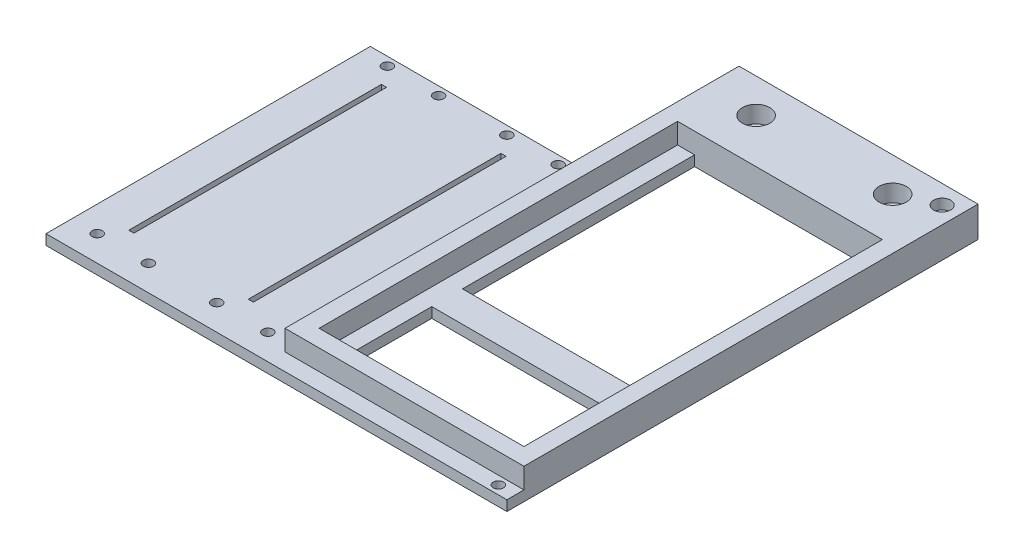
SolidWorks part; units mm, degrees
ref_plane "Front Plane" through (0, 0, 0) normal (0, 0, 1) x (1, 0, 0)
ref_plane "Top Plane" through (0, 0, 0) normal (0, 1, 0) x (1, 0, 0)
ref_plane "Right Plane" through (0, 0, 0) normal (1, 0, 0) x (0, 0, -1)
sketch "Sketch1" plane through (0, 0, 0) normal (0, 1, 0) x (1, 0, 0)
  line L0 (-30, 40) -> (30, 40)
  line L1 (-35, -65) -> (35, -65)
  line L2 (-35, -65) -> (-35, 65)
  line L3 (-35, 65) -> (35, 65)
  line L4 (35, -65) -> (35, 65)
  line L5 (-35, -65) -> (35, 65) construction
  line L6 (-35, 65) -> (35, -65) construction
  line L7 (-35, -65) -> (-30, -65)
  line L8 (-35, -65) -> (-35, 65)
  line L9 (-35, 65) -> (-30, 65)
  line L10 (-30, -65) -> (-30, 65)
  line L11 (35, 65) -> (30, 65)
  line L12 (35, 65) -> (35, -65)
  line L13 (35, -65) -> (30, -65)
  line L14 (30, 65) -> (30, -65)
  line L15 (-30, -65) -> (30, -65)
  line L16 (-30, -65) -> (-30, -60)
  line L17 (-30, -60) -> (30, -60)
  line L18 (30, -65) -> (30, -60)
  line L19 (-95, 22.5) -> (-75, 22.5) construction
  line L20 (-35, -65) -> (-100, -65)
  line L21 (-35, -65) -> (-35, 25)
  line L22 (-35, 25) -> (-100, 25)
  line L23 (-100, -65) -> (-100, 25)
  line L24 (-95, -65) -> (-75, -65)
  line L25 (-95, -65) -> (-95, 25)
  line L26 (-95, 25) -> (-75, 25)
  line L27 (-75, -65) -> (-75, 25)
  line L28 (-85, 22.5) -> (-85, 25) construction
  line L29 (-100, -20) -> (-35, -20) construction
  line L30 (-67.5, -65) -> (-67.5, 25) construction
  line L31 (-40, 25) -> (-60, 25)
  line L32 (-60, -65) -> (-60, 25)
  line L33 (-40, -65) -> (-60, -65)
  line L34 (-40, -65) -> (-40, 25)
  line L35 (-53.75, -57) -> (-53.75, 17)
  line L36 (-88.75, -57) -> (-87.25, -57)
  line L37 (-88.75, -57) -> (-88.75, 17)
  line L38 (-88.75, 17) -> (-87.25, 17)
  line L39 (-87.25, -57) -> (-87.25, 17)
  line L40 (-88.75, -57) -> (-87.25, 17) construction
  line L41 (-88.75, 17) -> (-87.25, -57) construction
  line L42 (-53.75, -57) -> (-52.25, -57)
  line L43 (-52.25, -57) -> (-52.25, 17)
  line L44 (-53.75, 17) -> (-52.25, 17)
  line L46 (-25, -55) -> (25, -55)
  line L47 (-25, -55) -> (-25, 55)
  line L48 (-25, 55) -> (25, 55)
  line L49 (25, -55) -> (25, 55)
  line L50 (-25, -55) -> (25, 55) construction
  line L51 (-25, 55) -> (25, -55) construction
  line L52 (-25, -32) -> (25, -32)
  line L53 (-25, -32) -> (-25, -23)
  line L54 (-25, -23) -> (25, -23)
  line L55 (25, -32) -> (25, -23)
  line L56 (-30, 65) -> (25, 65)
  line L57 (-30, 65) -> (-30, 45)
  line L58 (-30, 45) -> (25, 45)
  line L59 (25, 65) -> (25, 45)
  line L60 (25, 45) -> (30, 45)
  line L61 (25, 45) -> (25, 55)
  line L62 (25, 55) -> (30, 55)
  line L63 (30, 45) -> (30, 55)
  circle A0 centre (-92.5, 22.5) radius 1.5
  circle A1 centre (-77.5, 22.5) radius 1.5
  circle A2 centre (-77.5, -62.5) radius 1.5
  circle A3 centre (-92.5, -62.5) radius 1.5
  circle A4 centre (-42.5, -62.5) radius 1.5
  circle A5 centre (-57.5, -62.5) radius 1.5
  circle A6 centre (-57.5, 22.5) radius 1.5
  circle A7 centre (-42.5, 22.5) radius 1.5
  point P0 (0, 0)
  point P49 (-88, -20)
  point P54 (0, 0)
  dimension "D11" = 2.5
  dimension "D1" = 70
  dimension "D2" = 130
  dimension "D3" = 5
  dimension "D4" = 5
  dimension "D5" = 5
  dimension "D6" = 100
  dimension "D7" = 90
  dimension "D8" = 135
  dimension "D9" = 5
  dimension "D10" = 90
  dimension "D12" = 2.5
  dimension "D13" = 20
  dimension "D14" = 15
  dimension "D15" = 1.5
  dimension "D16" = 74
  dimension "D17" = 7
  dimension "D18" = 2
  dimension "D19" = 5
  dimension "D20" = 5
  dimension "D21" = 9
  dimension "D22" = 23
  dimension "D23" = 5
extrude "Boss-Extrude1" add sketch "Sketch1" along normal blind 9 contours L1 L10 L3 L2 | L17 L10 L1 L14 | L3 L14 L1 L4 | L59 L3 L10 L58 L47 L48 | L47 L58 L49 L48 | L59 L62 L14 L3 | L62 L49 L60 L14 region at (-32.5, 0, 0) region at (0, 0, 62.5) region at (-4.5833, 0, -59.1667) region at (0, 0, -50) region at (32.5, 0, 0) region at (27.5, 0, -50) region at (27.5, 0, -60)
extrude "Boss-Extrude2" add sketch "Sketch1<3>" along normal blind 3 contours L10 L17 L14 L0 | L14 L3 L10 L0 | L20 L25 L22 L23 | L20 L27 L22 L25 A1 A0 A2 A3 | L20 L32 L22 L27 | L20 L34 L22 L32 A5 A4 A6 A7 | L34 L20 L2 L22 | L54 L47 L52 L49 | L58 L10 L0 L47 | L60 L49 L0 L14 region at (-27.5, 0, -42.5) region at (-27.5, 0, -38.8338) region at (27.5, 0, -42.5) region at (0, 0, 27.5) region at (-37.5, 0, 20) region at (27.5, 0, -60) region at (-49.7995, 0, 20) region at (-67.5, 0, 20) region at (-84.7995, 0, 20) region at (-97.5, 0, 20)
sketch "Sketch1<3>" plane through (0, 0, 0) normal (0, 1, 0) x (1, 0, 0) same geometry as "Sketch1"
sketch "Sketch2" plane through (0, 0, 0) normal (0, 1, 0) x (1, 0, 0)
  line L0 (-35, -65) -> (35, -65) construction
  line L1 (-35, -65) -> (-100, -65) construction
  line L2 (-35, -65) -> (35, -65)
  line L3 (-35, -65) -> (-100, -65)
  line L4 (35, -67.5) -> (16.5103, -67.5) construction
  line L5 (35, -65) -> (-100, -65)
  line L6 (35, -65) -> (35, -70)
  line L7 (35, -70) -> (-100, -70)
  line L8 (-100, -65) -> (-100, -70)
  circle A0 centre (30, -67.5) radius 1.5
  dimension "D2" = 5
  dimension "D1" = 5
extrude "Boss-Extrude3" add sketch "Sketch2" along normal blind 3 contours L3 L8 L7 L6 L2 region at (-33.1614, 0, 67.5)
sketch "Sketch3" plane through (0, 9, 0) normal (0, 1, 0) x (1, 0, 0)
  line L0 (0, 65) -> (0, 25.4695) construction
  line L1 (-35, 65) -> (35, 65) construction
  line L2 (-35, 65) -> (35, 65)
  line L3 (-22.9804, 58) -> (23.7883, 58) construction
  line L4 (35, -65) -> (35, 65) construction
  line L5 (35, -65) -> (35, 65)
  line L6 (30, 60) -> (30, 65) construction
  line L7 (35, 60) -> (25, 60)
  line L8 (35, 60) -> (35, 65)
  line L9 (35, 65) -> (25, 65)
  line L10 (25, 60) -> (25, 65)
  circle A0 centre (-20, 58) radius 4
  circle A1 centre (20, 58) radius 4
  circle A2 centre (30, 62.5) radius 1.5
  circle A3 centre (30, 62.5) radius 2.5
  dimension "D1" = 40
  dimension "D2" = 8
  dimension "D3" = 7
  dimension "D4" = 5
  dimension "D5" = 10
extrude "Cut-Extrude1" cut sketch "Sketch3" against normal blind 5 contours A0 | A1
extrude "Cut-Extrude2" cut sketch "Sketch3<3>" against normal blind 20 contours A2 region at (30, 9, -62.5)
sketch "Sketch3<3>" plane through (0, 9, 0) normal (0, 1, 0) x (1, 0, 0) same geometry as "Sketch3"
sketch "Sketch4" plane through (0, 0, -65) normal (0, 0, -1) x (-1, 0, 0)
  line L4 (-35, 9) -> (-35, 0)
  line L5 (-35, 0) -> (35, 0)
  line L6 (35, 0) -> (35, 9)
  line L7 (35, 9) -> (-35, 9)
  line L8 (-35, 9) -> (-35, 0)
  line L9 (-35, 0) -> (35, 0)
  line L10 (35, 0) -> (35, 9)
  line L11 (35, 9) -> (-35, 9)
  dimension "D1" = 0
extrude "Boss-Extrude4" add sketch "Sketch4" along normal blind 3
extrude "Cut-Extrude5" cut sketch "Sketch3<6>" against normal blind 3 contours A3 A2 region at (31.7178, 9, -64.2178)
sketch "Sketch3<6>" plane through (0, 9, 0) normal (0, 1, 0) x (1, 0, 0) same geometry as "Sketch3"
